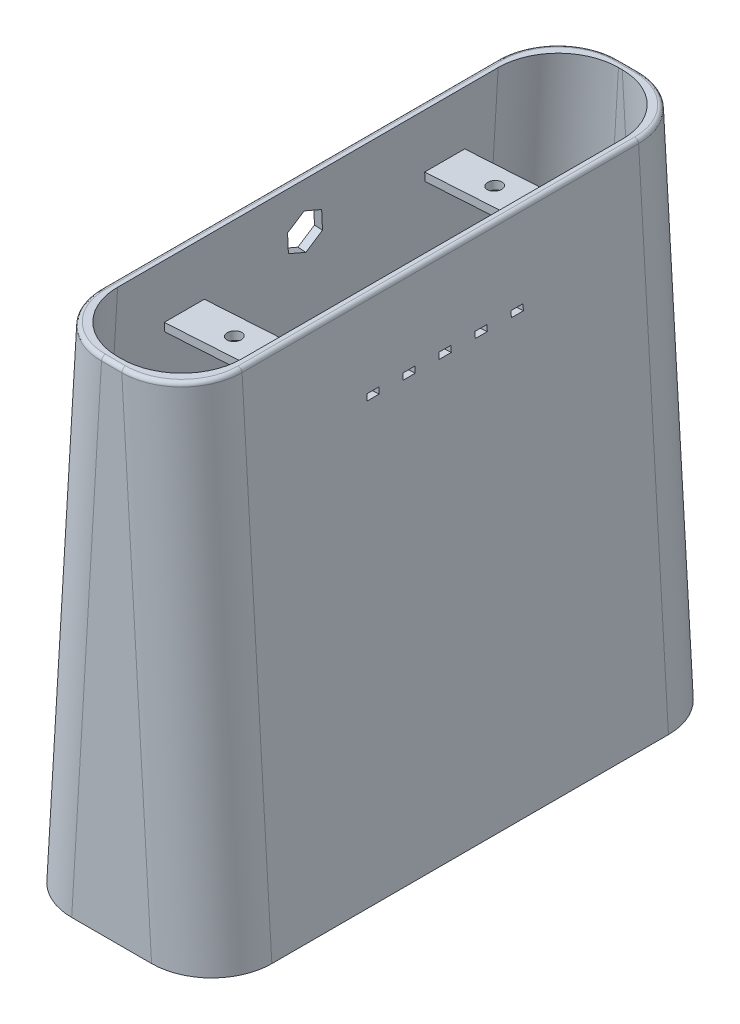
SolidWorks part; units mm, degrees
ref_plane "Plan de face" through (0, 0, 0) normal (0, 0, 1) x (1, 0, 0)
ref_plane "Plan de dessus" through (0, 0, 0) normal (0, 1, 0) x (1, 0, 0)
ref_plane "Plan de droite" through (0, 0, 0) normal (1, 0, 0) x (0, 0, -1)
sketch "Esquisse9" plane through (0, 0, 0) normal (0, 0, 1) x (1, 0, 0)
  line L0 (-42.5, 125) -> (-50, 0)
  line L1 (-50, 0) -> (0, 0)
  line L2 (0, 0) -> (-7.5, 125)
  line L3 (-7.5, 125) -> (-42.5, 125)
  dimension "D1" = 50
  dimension "D2" = 35
  dimension "D3" = 125
extrude "Boss.-Extru.1" add sketch "Esquisse9" along normal blind 2
sketch "Esquisse10" plane through (0, 0, 0) normal (0, 0, -1) x (-1, 0, 0)
  line L0 (9.5036, 125) -> (2.0036, 0)
  line L1 (2.0036, 0) -> (47.9964, 0)
  line L2 (47.9964, 0) -> (40.4964, 125)
  line L3 (40.4964, 125) -> (9.5036, 125)
  line L4 (42.5, 125) -> (50, 0) construction
  line L5 (0, 0) -> (7.5, 125) construction
  line L12 (42.5, 125) -> (7.5, 125)
  line L13 (7.5, 125) -> (0, 0)
  line L14 (0, 0) -> (50, 0)
  line L15 (50, 0) -> (42.5, 125)
  line L16 (42.5, 125) -> (7.5, 125)
  line L17 (7.5, 125) -> (0, 0)
  line L18 (0, 0) -> (50, 0)
  line L19 (50, 0) -> (42.5, 125)
  line M9 (42.5, 125) -> (7.5, 125)
  line M10 (7.5, 125) -> (0, 0)
  line M11 (0, 0) -> (50, 0)
  line M12 (50, 0) -> (42.5, 125)
  dimension "D3" = 2
  dimension "D4" = 2
  dimension "D5" = 0
extrude "Boss.-Extru.2" add sketch "Esquisse10" along normal blind 125 contours L0 M9 M10 M11 | L2 M11 M12 M9
sketch "Esquisse11" plane through (0, 0, -125) normal (0, 0, -1) x (-1, 0, 0)
  line L0 (7.5, 125) -> (42.5, 125)
  line L1 (42.5, 125) -> (50, 0)
  line L2 (50, 0) -> (0, 0)
  line L3 (7.5, 125) -> (0, 0)
  line L4 (9.5036, 125) -> (2.0036, 0)
  line L5 (40.4964, 125) -> (47.9964, 0)
extrude "Boss.-Extru.3" add sketch "Esquisse11" along normal blind 2 contours L2 L3 L0 L1
sketch "Esquisse13" plane through (0, 0, 0) normal (0.9982, 0.0599, 0) x (0, 0, -1)
  line L0 (-2, 0) -> (-2, 125.2248) construction
  line L1 (46, 105.2248) -> (43, 105.2248)
  line L2 (46, 105.2248) -> (46, 103.7248)
  line L3 (46, 103.7248) -> (43, 103.7248)
  line L4 (43, 105.2248) -> (43, 103.7248)
  line L5 (55, 105.2248) -> (52, 105.2248)
  line L6 (55, 105.2248) -> (55, 103.7248)
  line L7 (55, 103.7248) -> (52, 103.7248)
  line L8 (52, 105.2248) -> (52, 103.7248)
  line L9 (64, 105.2248) -> (61, 105.2248)
  line L10 (64, 105.2248) -> (64, 103.7248)
  line L11 (64, 103.7248) -> (61, 103.7248)
  line L12 (61, 105.2248) -> (61, 103.7248)
  line L13 (73, 105.2248) -> (70, 105.2248)
  line L14 (73, 105.2248) -> (73, 103.7248)
  line L15 (73, 103.7248) -> (70, 103.7248)
  line L16 (70, 105.2248) -> (70, 103.7248)
  line L17 (82, 105.2248) -> (79, 105.2248)
  line L18 (82, 105.2248) -> (82, 103.7248)
  line L19 (82, 103.7248) -> (79, 103.7248)
  line L20 (79, 105.2248) -> (79, 103.7248)
  line L21 (127, 125.2248) -> (127, 0) construction
  line L22 (-2, 125.2248) -> (127, 125.2248) construction
  dimension "D1" = 3
  dimension "D2" = 1.5
  dimension "D3" = 6
  dimension "D4" = 45
  dimension "D5" = 45
  dimension "D6" = 6
  dimension "D7" = 6
  dimension "D8" = 20
extrude "Enlèv. mat.-Extru.2" cut sketch "Esquisse13" against normal blind 2
sketch "Esquisse18" plane through (-47.8242, 2.8695, 0) normal (0.9982, -0.0599, 0) x (0, 0, -1)
  line L0 (0, -2.8746) -> (0, 122.3502) construction
  line L1 (25, 12.1254) -> (30, 12.1254)
  line L2 (25, 12.1254) -> (25, 7.1254)
  line L3 (25, 7.1254) -> (30, 7.1254)
  line L4 (30, 12.1254) -> (30, 7.1254)
  line L5 (95, 12.1254) -> (100, 12.1254)
  line L6 (95, 12.1254) -> (95, 7.1254)
  line L7 (95, 7.1254) -> (100, 7.1254)
  line L8 (100, 12.1254) -> (100, 7.1254)
  line L9 (125, -2.8746) -> (125, 122.3502) construction
  line L10 (125, -2.8746) -> (0, -2.8746) construction
  dimension "D1" = 25
  dimension "D2" = 25
  dimension "D3" = 5
  dimension "D4" = 10
  dimension "D5" = 10
extrude "Boss.-Extru.8" add sketch "Esquisse18" along normal blind 6.5
fillet "Congé2" radius 15 7 edges at (-5.7536, 62.5, 0) (-44.2464, 62.5, 0) (-44.2464, 62.5, -125) (-5.7536, 62.5, -125) (-3.75, 62.5, -127) (-46.25, 62.5, 2) (-3.75, 62.5, 2)
fillet "Congé3" radius 15 1 edges at (-46.25, 62.5, -127)
sketch "Esquisse19" plane through (0, 0, -127) normal (0, 0, -1) x (-1, 0, 0)
  line L0 (34.973, 0) -> (15.027, 0) construction
  line L1 (19.013, 27.5) -> (31.013, 27.5)
  line L2 (19.013, 27.5) -> (19.013, 7.5)
  line L3 (19.013, 7.5) -> (31.013, 7.5)
  line L4 (31.013, 27.5) -> (31.013, 7.5)
  dimension "D1" = 12
  dimension "D2" = 20
  dimension "D3" = 7.5
  dimension "D4" = 3.96
extrude "Enlèv. mat.-Extru.3" cut sketch "Esquisse19" against normal blind 6.5
sketch "Esquisse21" plane through (0, 0, -127) normal (0, 0, -1) x (-1, 0, 0)
  line L0 (31.013, 27.5) -> (19.013, 27.5) construction
  line L1 (23.237, 41.5) -> (26.737, 41.5)
  line L2 (23.237, 41.5) -> (23.237, 32.5)
  line L3 (23.237, 32.5) -> (26.737, 32.5)
  line L4 (26.737, 41.5) -> (26.737, 32.5)
  dimension "D1" = 3.5
  dimension "D2" = 9
  dimension "D3" = 5
  dimension "D4" = 8.21
extrude "Enlèv. mat.-Extru.4" cut sketch "Esquisse21" against normal blind 6.5
fillet "Congé4" radius 1 4 edges at (-26.737, 41.5, -126) (-23.237, 41.5, -126) (-23.237, 32.5, -126) (-26.737, 32.5, -126)
sketch "Esquisse22" plane through (0, 0, -125) normal (0, 0, 1) x (1, 0, 0)
  line L0 (-19.013, 27.5) -> (-31.013, 27.5) construction
  line L1 (-18.013, 6.5) -> (-32.013, 6.5)
  line L2 (-18.013, 6.5) -> (-18.013, 28.5)
  line L3 (-18.013, 28.5) -> (-32.013, 28.5)
  line L4 (-32.013, 6.5) -> (-32.013, 28.5)
  line L5 (-31.013, 7.5) -> (-19.013, 7.5) construction
  line L6 (-19.013, 7.5) -> (-19.013, 27.5) construction
  line L7 (-31.013, 27.5) -> (-31.013, 7.5) construction
  dimension "D1" = 1
  dimension "D2" = 1
  dimension "D3" = 1
  dimension "D4" = 1
extrude "Enlèv. mat.-Extru.5" cut sketch "Esquisse22" against normal blind 0.5
sketch "Esquisse23" plane through (-1.9964, -0.1198, 0) normal (-0.9982, -0.0599, 0) x (0, 0, 1)
  line L0 (-110, 125.3448) -> (-15, 125.3448) construction
  line L1 (-90, 115.3448) -> (-100, 115.3448)
  line L2 (-90, 115.3448) -> (-90, 113.3448)
  line L3 (-90, 113.3448) -> (-100, 113.3448)
  line L4 (-100, 115.3448) -> (-100, 113.3448)
  line L5 (-25, 115.3448) -> (-35, 115.3448)
  line L6 (-25, 115.3448) -> (-25, 113.3448)
  line L7 (-25, 113.3448) -> (-35, 113.3448)
  line L8 (-35, 115.3448) -> (-35, 113.3448)
  line L9 (-110, 125.3448) -> (-110, 0.12) construction
  line L10 (-15, 0.12) -> (-15, 125.3448) construction
  dimension "D1" = 10
  dimension "D2" = 10
  dimension "D3" = 10
  dimension "D4" = 2
  dimension "D5" = 2
  dimension "D6" = 10
  dimension "D7" = 10
extrude "Boss.-Extru.9" add sketch "Esquisse23" along normal blind 30
sketch "Esquisse24" plane through (-47.8242, 2.8695, 0) normal (0.9982, -0.0599, 0) x (0, 0, -1)
  line L1 (15, -2.8746) -> (25, -2.8746)
  line L2 (15, -2.8746) -> (15, 2.1254)
  line L3 (15, 2.1254) -> (25, 2.1254)
  line L4 (25, -2.8746) -> (25, 2.1254)
  line L5 (110, -2.8746) -> (100, -2.8746)
  line L6 (110, -2.8746) -> (110, 2.1254)
  line L7 (110, 2.1254) -> (100, 2.1254)
  line L8 (100, -2.8746) -> (100, 2.1254)
  dimension "D1" = 10
  dimension "D2" = 10
  dimension "D3" = 5
  dimension "D4" = 5
extrude "Boss.-Extru.11" add sketch "Esquisse24" along normal blind 10
sketch "Esquisse25" plane through (-1.9964, -0.1198, 0) normal (-0.9982, -0.0599, 0) x (0, 0, 1)
  line L1 (-110, 0.12) -> (-100, 0.12)
  line L2 (-110, 0.12) -> (-110, 5.12)
  line L3 (-110, 5.12) -> (-100, 5.12)
  line L4 (-100, 0.12) -> (-100, 5.12)
  line L5 (-15, 0.12) -> (-25, 0.12)
  line L6 (-15, 0.12) -> (-15, 5.12)
  line L7 (-15, 5.12) -> (-25, 5.12)
  line L8 (-25, 0.12) -> (-25, 5.12)
  dimension "D1" = 10
  dimension "D2" = 10
  dimension "D3" = 5
  dimension "D4" = 5
sketch "Esquisse26" plane through (-6.7885, 113.1413, 0) normal (0.0599, -0.9982, 0) x (-0.9982, -0.0599, 0)
  line L0 (32, 25) -> (2, 25) construction
  line L1 (32, 90) -> (2, 90) construction
  line L2 (2, 35) -> (2, 25) construction
  circle A0 centre (19.5, 30) radius 1.75
  circle A1 centre (19.5, 95) radius 1.75
  dimension "D4" = 3.5
  dimension "D1" = 5
  dimension "D2" = 5
  dimension "D3" = 17.5
extrude "Enlèv. mat.-Extru.6" cut sketch "Esquisse26" against normal blind 10
sketch "Esquisse28" plane through (-49.8206, 2.9892, 0) normal (-0.9982, 0.0599, 0) x (0, 0, 1)
  line L0 (-13, 122.2302) -> (-112, 122.2302) construction
  line L1 (-66.4779, 113.1042) -> (-66.9779, 108.2222)
  line L2 (-66.9779, 108.2222) -> (-63, 105.3482)
  line L3 (-63, 105.3482) -> (-58.5221, 107.3562)
  line L4 (-58.5221, 107.3562) -> (-58.0221, 112.2381)
  line L5 (-58.0221, 112.2381) -> (-62, 115.1121)
  line L6 (-62, 115.1121) -> (-66.4779, 113.1042)
  line L7 (-13, -2.9946) -> (-13, 122.2302) construction
  circle A0 centre (-62.5, 110.2302) radius 4.25 construction
  dimension "D1" = 12
  dimension "D2" = 8.5
  dimension "D3" = 49.5
  dimension "D4" = 50
extrude "Enlèv. mat.-Extru.9" cut sketch "Esquisse28" against normal blind 6
fillet "Congé7" radius 1 8 edges at (-25, 125, -127) (-11.9013, 125, -122.6066) (-7.5, 125, -62.5) (-11.9013, 125, -2.3934) (-25, 125, 2) (-38.0987, 125, -2.3934) (-42.5, 125, -62.5) (-38.0987, 125, -122.6066)
extrude "Boss.-Extru.12" add sketch "Esquisse25" along normal blind 10
sketch "Esquisse34" plane through (-0.1722, -2.8695, 0) normal (-0.0599, -0.9982, 0) x (-0.9982, 0.0599, 0)
  line L0 (37.9102, 15) -> (47.9102, 15) construction
  line L1 (37.9102, 15) -> (37.9102, 25) construction
  line L3 (37.9102, 110) -> (47.9102, 110) construction
  circle A0 centre (42.9102, 20) radius 1.75
  circle A3 centre (42.9102, 105) radius 1.75
  dimension "D1" = 3.5
  dimension "D2" = 5
  dimension "D3" = 5
  dimension "D5" = 5
extrude "Enlèv. mat.-Extru.16" cut sketch "Esquisse34" against normal blind 10
sketch "Esquisse35" plane through (-0.0072, 0.1198, 0) normal (0.0599, -0.9982, 0) x (-0.9982, -0.0599, 0)
  line L0 (12, 15) -> (2, 15) construction
  line L2 (12, 25) -> (12, 15) construction
  line L3 (12, 100) -> (2, 100) construction
  line L6 (12, 110) -> (12, 100) construction
  circle A0 centre (7, 20) radius 1.75
  circle A1 centre (7, 105) radius 1.75
  dimension "D1" = 3.5
  dimension "D2" = 5
  dimension "D3" = 5
  dimension "D4" = 5
  dimension "D5" = 5
extrude "Enlèv. mat.-Extru.17" cut sketch "Esquisse35" against normal blind 10
thread "Filetage3" pitch 0.8 start angle 0, offset 1, length 0, pitch 0.8, diameter 3.5
ref_plane "Plan3" through (-41.3184, -1.4025, -20) normal (0, 0, 1) x (0.9982, -0.0599, 0)
sketch "Profil de filetage3" plane through (-41.3184, -1.4025, -20) normal (0, 0, 1) x (0.9982, -0.0599, 0)
  line L0 (0, 0) -> (0, 0.8) construction
  line L1 (0, 0) -> (0.433, 0.25)
  line L2 (0.433, 0.25) -> (0.433, 0.35)
  line L3 (0.433, 0.35) -> (0, 0.6)
  line L4 (0.433, 0.3) -> (0, 0.3) construction
  line L11 (0, 0) -> (0, 0.6)
  point P2 (0, 0)
  dimension "Pitch" = 0.8
  dimension "Profile_Angle" = 60
  dimension "Profile_Land" = 0.1
  dimension "Profile_Height" = 0.433
thread "Filetage4" pitch 0.8 profile "Profil de filetage4" start angle 0, offset 1, length 0, pitch 0.8, diameter 3.5
ref_plane "Plan4" through (-44.3929, 5.7946, -105) normal (0, 0, 1) x (-0.9982, 0.0599, 0)
sketch "Profil de filetage4" plane through (-44.3929, 5.7946, -105) normal (0, 0, 1) x (-0.9982, 0.0599, 0)
  line L0 (0, 0) -> (0, 0.8) construction
  line L1 (0, 0) -> (0.433, 0.25)
  line L2 (0.433, 0.25) -> (0.433, 0.35)
  line L3 (0.433, 0.35) -> (0, 0.6)
  line L4 (0.433, 0.3) -> (0, 0.3) construction
  line L11 (0, 0) -> (0, 0.6)
  point P2 (0, 0)
  dimension "Pitch" = 0.8
  dimension "Profile_Angle" = 60
  dimension "Profile_Land" = 0.1
  dimension "Profile_Height" = 0.433
thread "Filetage5" pitch 0.8 profile "Profil de filetage5" start angle 0, offset 1, length 0, pitch 0.8, diameter 3.5
ref_plane "Plan5" through (-9.1008, 5.585, -20) normal (0, 0, 1) x (-0.9982, -0.0599, 0)
sketch "Profil de filetage5" plane through (-9.1008, 5.585, -20) normal (0, 0, 1) x (-0.9982, -0.0599, 0)
  line L0 (0, 0) -> (0, 0.8) construction
  line L1 (0, 0) -> (0.433, 0.25)
  line L2 (0.433, 0.25) -> (0.433, 0.35)
  line L3 (0.433, 0.35) -> (0, 0.6)
  line L4 (0.433, 0.3) -> (0, 0.3) construction
  line L11 (0, 0) -> (0, 0.6)
  point P2 (0, 0)
  dimension "Pitch" = 0.8
  dimension "Profile_Angle" = 60
  dimension "Profile_Land" = 0.1
  dimension "Profile_Height" = 0.433
thread "Filetage6" pitch 0.8 profile "Profil de filetage6" start angle 0, offset 1, length 0, pitch 0.8, diameter 3.5
ref_plane "Plan6" through (-9.1008, 5.585, -105) normal (0, 0, 1) x (-0.9982, -0.0599, 0)
sketch "Profil de filetage6" plane through (-9.1008, 5.585, -105) normal (0, 0, 1) x (-0.9982, -0.0599, 0)
  line L0 (0, 0) -> (0, 0.8) construction
  line L1 (0, 0) -> (0.433, 0.25)
  line L2 (0.433, 0.25) -> (0.433, 0.35)
  line L3 (0.433, 0.35) -> (0, 0.6)
  line L4 (0.433, 0.3) -> (0, 0.3) construction
  line L11 (0, 0) -> (0, 0.6)
  point P2 (0, 0)
  dimension "Pitch" = 0.8
  dimension "Profile_Angle" = 60
  dimension "Profile_Land" = 0.1
  dimension "Profile_Height" = 0.433
